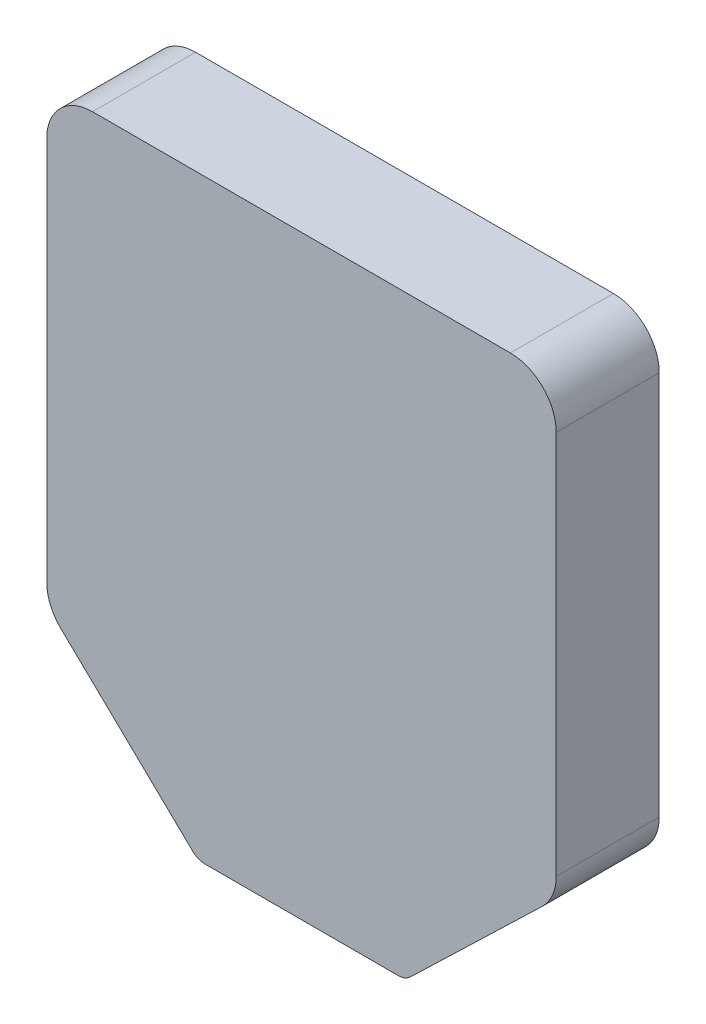
SolidWorks part; units mm, degrees
ref_plane "Front Plane" through (0, 0, 0) normal (0, 0, 1) x (1, 0, 0)
ref_plane "Top Plane" through (0, 0, 0) normal (0, 1, 0) x (1, 0, 0)
ref_plane "Right Plane" through (0, 0, 0) normal (1, 0, 0) x (0, 0, -1)
sketch "Palm_sketch" plane through (0, 0, 0) normal (0, 0, 1) x (1, 0, 0)
  line L0 (0, 78.6026) -> (0.0161, -25.3974)
  line L1 (-36.5, 78.6026) -> (36.5, 78.6026)
  line L2 (-44.5, 70.6026) -> (-44.5, 3.4047)
  line L3 (-16.8916, -25.3974) -> (16.9237, -25.3974)
  line L6 (-42.0464, -2.3605) -> (-18.9715, -24.5594)
  line L7 (42.05, -2.36) -> (19.005, -24.5581)
  line L8 (44.5, 70.6026) -> (44.5, 3.4018)
  line L9 (44.5, 70.6026) -> (44.5, 0)
  line L10 (44.5, 0) -> (19.005, -24.5581)
  arc A0 (-36.5, 78.6026) -> (-44.5, 70.6026) centre (-36.5, 70.6026) ccw
  arc A2 (36.5, 78.6026) -> (44.5, 70.6026) centre (36.5, 70.6026) cw
  arc A3 (-42.0464, -2.3605) -> (-44.5, 3.4047) centre (-36.5, 3.4047) cw
  arc A4 (42.05, -2.36) -> (44.5, 3.4018) centre (36.5, 3.4018) ccw
  arc A5 (-16.8916, -25.3974) -> (-18.9715, -24.5594) centre (-16.8916, -22.3974) cw
  arc A6 (19.005, -24.5581) -> (16.9237, -25.3974) centre (16.9237, -22.3974) cw
  dimension "D3" = 8
  dimension "D4" = 8
  dimension "D2" = 8
  dimension "D5" = 3
  dimension "D6" = 3
  dimension "D1" = 3
  dimension "D9" = 8
  dimension "D7" = 67.1978
  dimension "D8" = 33.8153
extrude "Palm_Body" add sketch "Palm_sketch" along normal mid plane 18 contours L8 A4 L7 A6 L3 A5 L6 A3 L2 A0 L1 A2
ref_axis "MCP_REFERENCE" through (36.5, 78.6026, 0) along (-1, 0, 0)
sketch "Sketch5" plane through (0, 78.6026, 0) normal (0, 1, 0) x (1, 0, 0)
  line L0 (-36.5, 0) -> (36.5, 0)
  line L1 (-36.5, -9) -> (-36.5, 9) construction
  line L2 (36.5, 0) -> (-36.5, 0) construction
  point P7 (-28, 0)
  point P8 (-28, 0)
  point P9 (-8.5, 0)
  point P10 (11, 0)
  point P11 (29, 0)
  dimension "D1" = 8.5
  dimension "D2" = 28
  dimension "D3" = 47.5
  dimension "D4" = 65.5
  dimension "D5" = 73
ref_axis "index" through (-28, 78.6026, 0) along (0, 1, 0)
ref_axis "middle" through (-8.5, 78.6026, 0) along (0, 1, 0)
ref_axis "ring" through (11, 78.6026, 0) along (0, 1, 0)
ref_axis "Little finger" through (29, 78.6026, 0) along (0, 1, 0)
sketch "Sketch6" plane through (-44.5, 0, 0) normal (-1, 0, 0) x (0, 0, 1)
  line L0 (0, 70.6026) -> (0, 3.4047)
  line L1 (9, 70.6026) -> (-9, 70.6026) construction
  line L2 (9, 3.4047) -> (-9, 3.4047) construction
  point P0 (0, 8.6026)
  dimension "D1" = 70
ref_axis "Thumb_CMC_Axis_1" through (-44.5, 8.6026, 0) along (1, 0, 0)
ref_axis "Thumb_CMC_Axis_2" through (-44.5, 8.6026, 0) along (0, 1, 0)
ref_point "wrist point"
ref_axis "Wrist_Axis" through (0.0161, -25.3974, 0) along (1, 0, 0)
ref_point "pinky"
ref_point "ring_point"
ref_point "middle_point"
ref_point "index_point"
ref_axis "index_point+right" through (-28, 78.6026, 0) along (1, 0, 0)
ref_axis "index_point+front" through (-28, 78.6026, 0) along (0, 0, 1)
ref_axis "middle+right" through (-8.5, 78.6026, 0) along (1, 0, 0)
ref_axis "middle_point+front" through (-8.5, 78.6026, 0) along (0, 0, 1)
ref_axis "ring_point+right" through (11, 78.6026, 0) along (1, 0, 0)
ref_axis "ring_point+front" through (11, 78.6026, 0) along (0, 0, 1)
ref_axis "pinky+right" through (29, 78.6026, 0) along (1, 0, 0)
ref_axis "pinky+front" through (29, 78.6026, 0) along (0, 0, 1)
